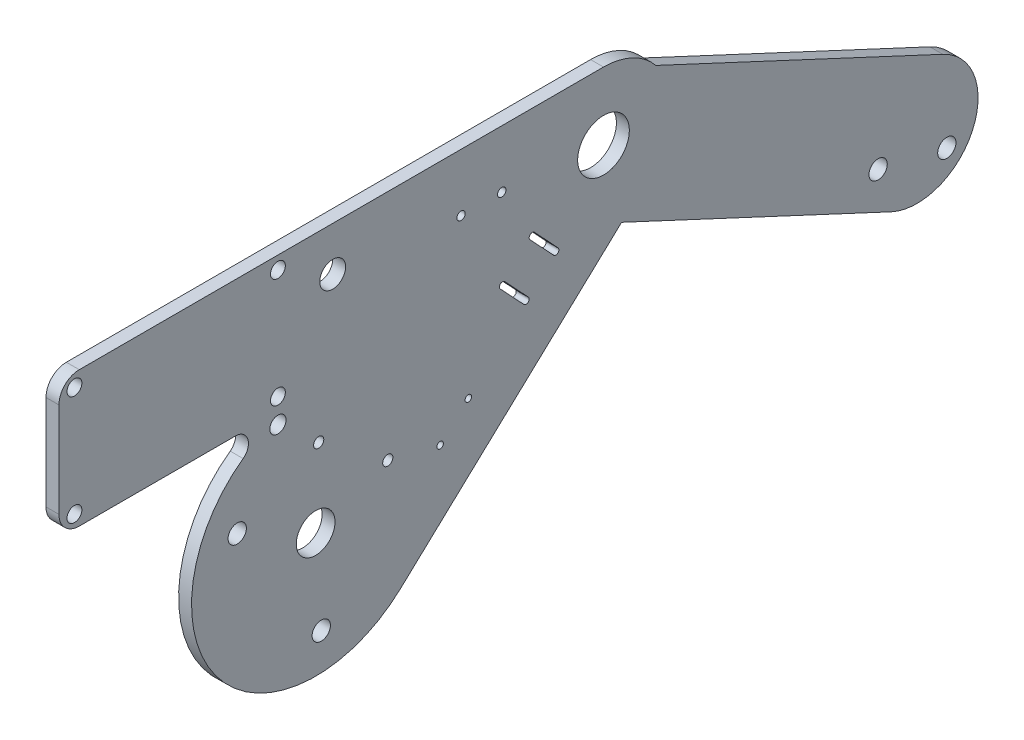
SolidWorks part; units mm, degrees
material "6061 Alloy"
ref_plane "Front Plane" through (0, 0, 0) normal (0, 0, 1) x (1, 0, 0)
ref_plane "Top Plane" through (0, 0, 0) normal (0, 1, 0) x (1, 0, 0)
ref_plane "Right Plane" through (0, 0, 0) normal (1, 0, 0) x (0, 0, -1)
sketch "Sketch1" plane through (0, 0, 0) normal (1, 0, 0) x (0, 0, -1)
  line L0 (-49.9001, -69.4268) -> (11.3662, -12.16)
  line L1 (-133.81, 16.645) -> (-76.19, 16.645)
  line L2 (-133.81, 16.645) -> (-133.81, -16.645)
  line L3 (-133.81, -16.645) -> (-76.19, -16.645)
  line L4 (-76.19, 16.645) -> (-76.19, -16.645)
  line L5 (-130, 13.475) -> (-80, 13.475)
  line L6 (-130, 13.475) -> (-130, -13.475)
  line L7 (-130, -13.475) -> (-80, -13.475)
  line L8 (-80, 13.475) -> (-80, -13.475)
  line L9 (-76.19, 16.645) -> (0, 16.645)
  line L10 (-83.2811, -19.3484) -> (-6.8511, 15.1697)
  line L11 (-130, -13.475) -> (-130, -19.435)
  line L12 (-80, -13.475) -> (-80, -19.435)
  line L13 (-76.19, -16.645) -> (0, -16.645)
  circle A0 centre (0, 0) radius 6.35
  circle A1 centre (-70.7273, -47.145) radius 4.7625
  circle A2 centre (-70.7273, -47.145) radius 23.015 construction
  circle A3 centre (-70.7273, -47.145) radius 30.5
  circle A4 centre (0, 0) radius 16.645
  circle A5 centre (-130, -19.435) radius 2
  circle A6 centre (-80, -19.435) radius 2
  point P4 (-133.81, 0)
  point P12 (-130, 0)
  dimension "D6" = 12.7
  dimension "D7" = 9.525
  dimension "D8" = 46.03
  dimension "D9" = 61
  dimension "D11" = 0
  dimension "D14" = 4
  dimension "D1" = 33.29
  dimension "D2" = 80
  dimension "D3" = 26.95
  dimension "D4" = 50
  dimension "D5" = 3.81
  dimension "D10" = 85
  dimension "D12" = 3.81
  dimension "D13" = 5.96
extrude "Boss-Extrude1" add sketch "Sketch1" along normal mid plane 3.175 contours A6 A3 A1 | A4 L13 A3 L0 | A4 A0 | A4 L10 L4 L13 | A4 L9 L4 L10 | L8 L12 L3 L10 L4 L1 L2 L11 L6 L5 | L8 L5 L6 L7 | L12 L7 L11 L3 | A6 A3 L13 L3 L10 | L10 L3 L4 | A3 A6 | A3 A6 L10 L12 | L10 A6 A3 L12 | A6 L10 A3 region at (0, -30.4378, 28.398) region at (0, -63.5833, 95.3881) region at (0, -15.0453, -5.9367) region at (0, -18.8843, 82.226) region at (0, -7.4928, 34.7947) region at (0, -18.2558, 80.7031) region at (0, -19.6484, 79.9286) region at (0, -17.0177, 76.5839) region at (0, 5.7227, 51.9516) region at (0, -17.8085, 79.5096) region at (0, -16.4786, 76.5584) region at (0, -15.7889, 77.0165) region at (0, -15.06, 105) region at (0, 0, 105)
sketch "Sketch12" plane through (0, 0, 0) normal (1, 0, 0) x (0, 0, -1)
  line L0 (0, 0) -> (77.0362, -35.9226) construction
  line L1 (6.3393, 13.5946) -> (83.3754, -22.3279)
  line L2 (-6.3393, -13.5946) -> (70.6969, -49.5172)
  line L3 (-1000, 0) -> (49000, 0) construction
  line L5 (-4.9661, -14.2349) -> (77.7852, -34.0471) construction
  arc A0 (6.3393, 13.5946) -> (-6.3393, -13.5946) centre (0, 0) ccw
  arc A1 (70.6969, -49.5172) -> (83.3754, -22.3279) centre (77.0362, -35.9226) ccw
  circle A2 centre (0, 0) radius 6.35 construction
  circle A3 centre (0, 0) radius 6.35
  arc A5 (77.7852, -34.0471) -> (91.9205, -34.0633) centre (84.8868, -4.3854) ccw construction
  point P3 (38.5181, -17.9613)
  dimension "D1" = 85
  dimension "D2" = 30
  dimension "D3" = 25
extrude "Boss-Extrude2" add sketch "Sketch12" along normal mid plane 3.175 contours L2 A1 L1 A0 region at (0, -18.6882, -40.0769)
hole_wizard "#6 Clearance Hole1" positions "Sketch2" profile "Sketch3" hole size "#6" standard "ANSI Inch" end condition up to next
sketch "Sketch2" plane through (1.5875, 0, 0) normal (1, 0, 0) x (0, 0, -1)
  point P0 (-80, -13.475)
  point P3 (-80, 13.475)
  point P6 (-130, 13.475)
  point P9 (-130, -13.475)
sketch "Sketch3" plane through (1.5875, -13.475, 80) normal (0, 1, 0) x (0, 0, -1)
  line L0 (0, 0) -> (0, 3.175)
  line L1 (0, 3.175) -> (1.8288, 3.175)
  line L2 (1.8288, 3.175) -> (1.8288, 0)
  line L5 (1.8288, 0) -> (0, 0)
  line L11 (0, -6.35) -> (0, 107.95) construction
  dimension "Thru Hole Dia." = 3.6576
  dimension "Thru Hole Depth" = 3.175
hole_wizard "M3x0.5 Tapped Hole1" positions "Sketch4" profile "Sketch5" tap size "M3x0.5" standard "ANSI Metric" end condition up to next
sketch "Sketch4" plane through (1.5875, 0, 0) normal (1, 0, 0) x (0, 0, -1)
  line L7 (-70.7273, -47.145) -> (-41.414, -6.6391) construction
  line L9 (-69.9837, -28.2416) -> (-53.0036, -40.5297) construction
  point P121 (-61.4936, -34.3856)
  point P124 (-69.9837, -28.2416)
  point P127 (-53.0036, -40.5297)
  dimension "D1" = 20.96
  dimension "D2" = 15.75
  dimension "D3" = 135
  dimension "D4" = 50
sketch "Sketch5" plane through (1.5875, -40.5297, 53.0036) normal (0, 1, 0) x (0, 0, -1)
  line L0 (0, 0) -> (0, 3.175)
  line L1 (0, 3.175) -> (1.25, 3.175)
  line L2 (1.25, 3.175) -> (1.25, 0)
  line L5 (1.25, 0) -> (0, 0)
  line L11 (0, -6.35) -> (0, 107.95) construction
  dimension "Thru Tap Drill Dia." = 2.5
  dimension "Thru Tap Drill Depth" = 3.175
hole_wizard "M4 Clearance Hole1" positions "Sketch6" profile "Sketch7" hole size "M4" standard "ANSI Metric" end condition up to next
sketch "Sketch6" plane through (1.5875, 0, 0) normal (1, 0, 0) x (0, 0, -1)
  line L0 (-70.7273, -47.145) -> (-69.3449, -68.6005) construction
  line L1 (-70.7273, -47.145) -> (-89.9995, -37.6144) construction
  line L3 (-70.7273, -47.145) -> (0, 0) construction
  line L7 (77.0362, -35.9226) -> (84.3628, -42.7285) construction
  line L9 (77.0362, -35.9226) -> (67.4787, -38.8646) construction
  line L10 (77.0362, -35.9226) -> (0, 0) construction
  point P2 (-69.3449, -68.6005)
  point P16 (-89.9995, -37.6144)
  point P37 (67.4787, -38.8646)
  point P40 (84.3628, -42.7285)
  dimension "D1" = 21.5
  dimension "D2" = 120
  dimension "D3" = 120
  dimension "D4" = 120
  dimension "D5" = 10
  dimension "D6" = 17.89
  dimension "D7" = 0
sketch "Sketch7" plane through (1.5875, -42.7285, -84.3628) normal (0, 1, 0) x (0, 0, -1)
  line L0 (0, 0) -> (0, 3.175)
  line L1 (0, 3.175) -> (2.25, 3.175)
  line L2 (2.25, 3.175) -> (2.25, 0)
  line L5 (2.25, 0) -> (0, 0)
  line L11 (0, -6.35) -> (0, 107.95) construction
  dimension "Thru Hole Dia." = 4.5
  dimension "Thru Hole Depth" = 3.175
hole_wizard "M2x0.4 Tapped Hole1" positions "Sketch8" profile "Sketch9" tap size "M2x0.4" standard "ANSI Metric" end condition up to next
sketch "Sketch8" plane through (1.5875, 0, 0) normal (1, 0, 0) x (0, 0, -1)
  line L0 (-49.9001, -69.4268) -> (4.4493, -18.6254) construction
  line L2 (0, 0) -> (34142.961, -36527.4995) construction
  point P0 (-33.212, -37.2653)
  point P2 (-40.1523, -43.7524)
  dimension "D1" = 12.1
  dimension "D2" = 9.5
  dimension "D3" = 12.1
  dimension "D4" = 49.71
sketch "Sketch9" plane through (1.5875, -37.2653, 33.212) normal (0, 1, 0) x (0, 0, -1)
  line L0 (0, 0) -> (0, 3.175)
  line L1 (0, 3.175) -> (0.8, 3.175)
  line L2 (0.8, 3.175) -> (0.8, 0)
  line L5 (0.8, 0) -> (0, 0)
  line L11 (0, -6.35) -> (0, 107.95) construction
  dimension "Thru Tap Drill Dia." = 1.6
  dimension "Thru Tap Drill Depth" = 3.175
cosmetic thread "Hole Thread1" parameters "D2"=2
cosmetic thread "Hole Thread2" parameters "D2"=2
fillet "Fillet1" radius 5 2 edges at (0, -16.645, 133.81) (0, 16.645, 133.81)
fillet "Fillet2" radius 3.175 1 edges at (0, -16.645, 77.2953)
extrude "Cut-Extrude1" cut sketch "Sketch1<3>" against normal through all both and the other way through all contours A3 A6 | A3 A6 L10 L12 | L12 A6 L10 | L10 A6 A3 L12 | L10 A6 L12 region at (0, -17.9759, 80.8435) region at (0, -18.2558, 80.7031) region at (0, -19.6484, 79.9286) region at (0, -17.6074, 79.7609) region at (0, -17.8085, 79.5096)
sketch "Sketch1<3>" plane through (0, 0, 0) normal (1, 0, 0) x (0, 0, -1) same geometry as "Sketch1"
hole_wizard "1/4 (0.2500) Dowel Hole1" positions "Sketch10" profile "Sketch11" hole size "1/4" standard "ANSI Inch" end condition up to next
sketch "Sketch10" plane through (1.5875, 0, 0) normal (1, 0, 0) x (0, 0, -1)
  line L0 (-66.5458, 5.822) -> (0, 0) construction
  line L2 (-1000, 0) -> (49000, 0) construction
  point P0 (-66.5458, 5.822)
  dimension "D1" = 66.8
  dimension "D2" = 5
sketch "Sketch11" plane through (1.5875, 5.822, 66.5458) normal (0, 1, 0) x (0, 0, -1)
  line L0 (0, 0) -> (0, 3.175)
  line L1 (0, 3.175) -> (3.175, 3.175)
  line L2 (3.175, 3.175) -> (3.175, 0)
  line L5 (3.175, 0) -> (0, 0)
  line L11 (0, -6.35) -> (0, 107.95) construction
  dimension "Thru Hole Dia." = 6.35
  dimension "Thru Hole Depth" = 3.175
sketch "Sketch13" plane through (1.5875, 0, 0) normal (1, 0, 0) x (0, 0, -1)
  line L0 (-4.9661, -14.2349) -> (77.7852, -34.0471) construction
  line L1 (-4.9661, -14.2349) -> (77.7852, -34.0471)
  line L2 (-6.3393, -13.5946) -> (70.6969, -49.5172) construction
  line L3 (-4.9661, -14.2349) -> (70.6969, -49.5172)
  arc A0 (77.7852, -34.0471) -> (91.9205, -34.0633) centre (84.8868, -4.3854) ccw construction
  arc A1 (77.7852, -34.0471) -> (91.9205, -34.0633) centre (84.8868, -4.3854) ccw
  arc A2 (70.6969, -49.5172) -> (83.3754, -22.3279) centre (77.0362, -35.9226) ccw construction
  arc A3 (70.6969, -49.5172) -> (91.9205, -34.0633) centre (77.0362, -35.9226) ccw
extrude "Boss-Extrude3" [suppressed] add sketch "Sketch13" along normal blind 10
hole_wizard "Ø1.5mm Dowel Slot1" positions "Sketch14" profile "Sketch15" size "Ø1.5" standard "ANSI Metric" slot yes end condition up to next
sketch "Sketch14" plane through (1.5875, 0, 0) normal (1, 0, 0) x (0, 0, -1)
  line L0 (-18.5022, -24.1385) -> (-25.3308, -16.833) construction
  line L3 (-21.9165, -20.4858) -> (-14.611, -13.6572) construction
  line L6 (-49.9001, -69.4268) -> (4.4493, -18.6254) construction
  point P0 (-21.9165, -20.4858)
  point P4 (-14.611, -13.6572)
  dimension "D1" = 10
  dimension "D2" = 10
  dimension "D3" = 20
sketch "Sketch15" plane through (1.5875, -20.4858, 21.9165) normal (0, 1, 0) x (0, 0, -1)
  line L0 (0, 0) -> (0, 3.175)
  line L1 (0, 3.175) -> (0.75, 3.175)
  line L2 (0.75, 3.175) -> (0.75, 0)
  line L5 (0.75, 0) -> (0, 0)
  line L11 (0, -6.35) -> (0, 107.95) construction
  dimension "Thru Hole Dia." = 1.5
  dimension "Thru Hole Depth" = 3.175
hole_wizard "M2.5x0.45 Tapped Hole1" positions "Sketch16" profile "Sketch17" tap size "M2.5x0.45" standard "ANSI Metric" end condition up to next
sketch "Sketch16" plane through (1.5875, 0, 0) normal (1, 0, 0) x (0, 0, -1)
  line L0 (-128.81, 16.645) -> (0, 16.645) construction
  point P0 (-35, 2.5)
  point P2 (-25, 2.5)
  dimension "D1" = 10
  dimension "D2" = 14.145
  dimension "D3" = 25
sketch "Sketch17" plane through (1.5875, 2.5, 35) normal (0, 1, 0) x (0, 0, -1)
  line L0 (0, 0) -> (0, 3.175)
  line L1 (0, 3.175) -> (1.025, 3.175)
  line L2 (1.025, 3.175) -> (1.025, 0)
  line L5 (1.025, 0) -> (0, 0)
  line L11 (0, -6.35) -> (0, 107.95) construction
  dimension "Thru Tap Drill Dia." = 2.05
  dimension "Thru Tap Drill Depth" = 3.175
cosmetic thread "Hole Thread3" parameters "D2"=2.5
cosmetic thread "Hole Thread4" parameters "D2"=2.5
